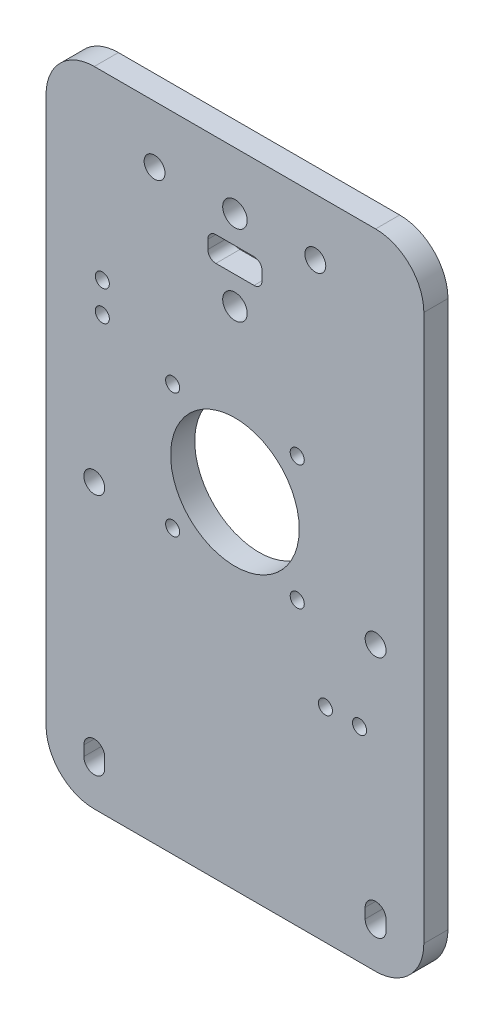
SolidWorks part; units mm, degrees
material "Acrylic (Medium-high impact)"
ref_plane "Спереди" through (0, 0, 0) normal (0, 0, 1) x (1, 0, 0)
ref_plane "Сверху" through (0, 0, 0) normal (0, 1, 0) x (1, 0, 0)
ref_plane "Справа" through (0, 0, 0) normal (1, 0, 0) x (0, 0, -1)
sketch "Model" plane through (0, 0, 0) normal (0, 0, 1) x (1, 0, 0)
  line L0 (-2.3021, 85.8) -> (5.2264, 85.8) construction
  line L1 (6.75, 135.8) -> (-6.75, 135.8) construction
  line L5 (0, 27.6115) -> (0, 21.6925) construction
  line L6 (-15.9818, 70.3) -> (-15.0228, 70.3) construction
  line L7 (-15.5, 9.9369) -> (-15.5, 9.0934) construction
  line L8 (15.5, 9.9369) -> (15.5, 9.0934) construction
  line L9 (15.9818, 70.3) -> (15.0228, 70.3) construction
  line L10 (15.9818, 101.3) -> (15.0228, 101.3) construction
  line L13 (-15.9818, 101.3) -> (-15.0228, 101.3) construction
  line L24 (-35, 37.2847) -> (-35, 77.3985) construction
  line L25 (-31.4983, 12.5) -> (-38.4, 12.5) construction
  line L26 (-31.4983, 10) -> (-38.4, 10) construction
  line L27 (-35, 12.5) -> (-35, 10) construction
  line L28 (-32.4, 12.5) -> (-32.4, 10)
  line L29 (-37.6, 12.5) -> (-37.6, 10)
  line L40 (31.4983, 10) -> (38.4, 10) construction
  line L41 (31.4983, 12.5) -> (38.4, 12.5) construction
  line L42 (35, 37.2847) -> (35, 77.3985) construction
  line L43 (35, 12.5) -> (35, 10) construction
  line L44 (32.4, 12.5) -> (32.4, 10)
  line L45 (37.6, 12.5) -> (37.6, 10)
  line L47 (-26.0102, 145.8) -> (26.0946, 145.8) construction
  line L48 (0, 129.408) -> (0, 90.7064) construction
  line L51 (-38.85, 70.45) -> (-29.8907, 70.45) construction
  line L53 (-16.3166, 125.8) -> (17.7871, 125.8) construction
  line L58 (38.85, 70.45) -> (29.8907, 70.45) construction
  line L4875 (-35, 160) -> (35, 160)
  line L4882 (47, 148) -> (47, 12)
  line L4889 (35, 0) -> (-35, 0)
  line L4896 (-47, 12) -> (-47, 148)
  line L5609 (6.75, 138.9) -> (-6.75, 138.9)
  line L5610 (-6.75, 138.9) -> (-6.75, 132.7)
  line L5611 (-6.75, 132.7) -> (6.75, 132.7)
  line L5612 (6.75, 132.7) -> (6.75, 138.9)
  line L6648 (-6.75, 138.9) -> (6.75, 138.9)
  line L6649 (6.75, 138.9) -> (6.75, 132.7)
  line L6650 (6.75, 132.7) -> (-6.75, 132.7)
  line L6651 (-6.75, 132.7) -> (-6.75, 138.9)
  arc A0 (-47, 12) -> (-35, 0) centre (-35, 12) ccw
  arc A1 (35, 0) -> (47, 12) centre (35, 12) ccw
  arc A2 (47, 148) -> (35, 160) centre (35, 148) ccw
  arc A3 (-35, 160) -> (-47, 148) centre (-35, 148) ccw
  circle A4 centre (0, 85.8) radius 16
  circle A5 centre (-15.5, 70.3) radius 1.75
  circle A6 centre (15.5, 70.3) radius 1.75
  circle A7 centre (15.5, 101.3) radius 1.75
  circle A8 centre (-15.5, 101.3) radius 1.75
  arc A13 (-32.4, 12.5) -> (-37.6, 12.5) centre (-35, 12.5) ccw
  arc A14 (-37.6, 10) -> (-32.4, 10) centre (-35, 10) ccw
  arc A19 (32.4, 12.5) -> (37.6, 12.5) centre (35, 12.5) cw
  arc A20 (37.6, 10) -> (32.4, 10) centre (35, 10) cw
  circle A29 centre (0, 145.8) radius 3.05
  circle A30 centre (-20, 145.8) radius 2.6
  circle A31 centre (20, 145.8) radius 2.6
  circle A32 centre (-35, 70.45) radius 2.6
  circle A33 centre (0, 125.8) radius 3.05
  circle A36 centre (35, 70.45) radius 2.6
  point P17 (0, 0)
  point P77 (-35, 11.25)
  point P114 (35, 11.25)
  point P127 (0, 160)
  dimension "D5" = 32
  dimension "D8" = 3.5
  dimension "D30" = 5.2
  dimension "D33" = 5.2
  dimension "D35" = 6.1
  dimension "D2" = 70
  dimension "D3" = 160
  dimension "D6" = 15.5
  dimension "D7" = 15.5
  dimension "D15" = 12
  dimension "D16" = 2.5
  dimension "D17" = 10
  dimension "D18" = 5.2
  dimension "D25" = 14.2
  dimension "D34" = 20
  dimension "D41" = 13.5
  dimension "D42" = 6.2
  dimension "D52" = 40
  dimension "D9" = 70
  dimension "D10" = 57.95
  dimension "D12" = 20
  dimension "D13" = 20
  dimension "D11" = 10
extrude "Base" add sketch "Model" along normal blind 6 contours L4875 A3 L4896 A0 L4889 A1 L4882 A2 L45 A20 L44 A19 region at (0, 158.1443, 0)
sketch "Sketch1" plane through (0, 0, 6) normal (0, 0, 1) x (1, 0, 0)
  line L1 (-35, 160) -> (35, 160) construction
  line L2 (-47, 12) -> (-47, 148) construction
  circle A0 centre (-33, 115) radius 1.75
  circle A1 centre (-33, 107.5) radius 1.75
  dimension "D1" = 3.5
  dimension "D3" = 7.5
  dimension "D4" = 14
  dimension "D5" = 45
extrude "SensorMount" cut sketch "Sketch1" against normal blind 10 contours A1 | A0
sketch "Sketch2" plane through (0, 0, 6) normal (0, 0, 1) x (1, 0, 0)
  line L0 (35, 0) -> (-35, 0) construction
  line L1 (-47, 12) -> (-47, 148) construction
  circle A0 centre (22.5, 50.76) radius 1.75
  circle A1 centre (31, 50.76) radius 1.75
  dimension "D1" = 3.5
  dimension "D3" = 8.5
  dimension "D4" = 50.76
  dimension "D5" = 69.5
extrude "CableMount" cut sketch "Sketch2" against normal blind 10 contours A0 | A1
fillet "FilletCableSlot" radius 2 4 edges at (6.75, 138.9, 3) (-6.75, 138.9, 3) (-6.75, 132.7, 3) (6.75, 132.7, 3)
equation "\"D11@Model\"=\"D34@Model\"/2"
